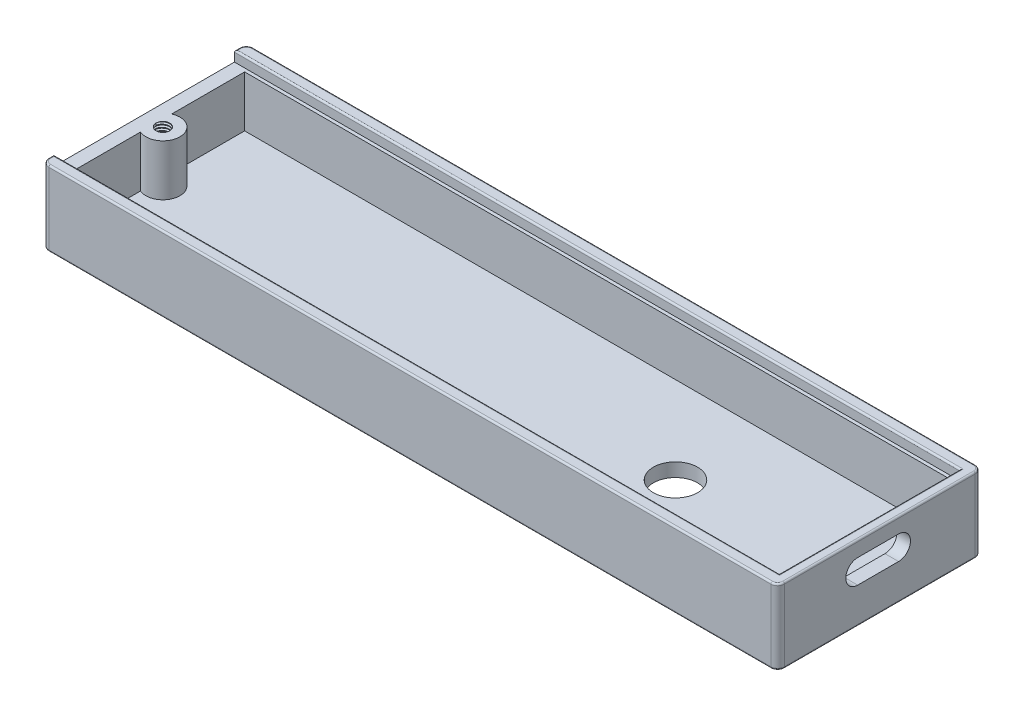
SolidWorks part; units mm, degrees
material "ABS"
ref_plane "Front Plane" through (0, 0, 0) normal (0, 0, 1) x (1, 0, 0)
ref_plane "Top Plane" through (0, 0, 0) normal (0, 1, 0) x (1, 0, 0)
ref_plane "Right Plane" through (0, 0, 0) normal (1, 0, 0) x (0, 0, -1)
sketch "Sketch1" plane through (0, 0, 0) normal (0, 1, 0) x (1, 0, 0)
  line L1 (0, 0) -> (108, 0)
  line L2 (0, 0) -> (0, -30)
  line L3 (0, -30) -> (108, -30)
  line L4 (108, 0) -> (108, -30)
  dimension "D1" = 108
  dimension "D2" = 30
extrude "Boss-Extrude1" add sketch "Sketch1" against normal blind 11
sketch "Sketch2" plane through (0, 0, 0) normal (0, 1, 0) x (1, 0, 0)
  line L0 (0, -30) -> (108, -30) construction
  line L1 (0, -1.75) -> (106.5, -1.75)
  line L2 (0, -1.75) -> (0, -28.25)
  line L3 (0, -28.25) -> (106.5, -28.25)
  line L4 (106.5, -1.75) -> (106.5, -28.25)
  line L6 (108, -30) -> (108, 0) construction
  line L8 (0, 0) -> (0, -30) construction
  line L10 (108, 0) -> (0, 0) construction
  dimension "D1" = 1.75
  dimension "D2" = 1.75
  dimension "D3" = 1.5
extrude "Cut-Extrude1" cut sketch "Sketch2" against normal blind 1.5
sketch "Sketch3" plane through (0, 0, 0) normal (0, 1, 0) x (1, 0, 0)
  line L0 (106.5, -1.75) -> (0, -1.75) construction
  line L1 (2, -2.25) -> (106, -2.25)
  line L2 (2, -2.25) -> (2, -27.75)
  line L3 (2, -27.75) -> (106, -27.75)
  line L4 (106, -2.25) -> (106, -27.75)
  line L5 (106.5, -28.25) -> (106.5, -1.75) construction
  line L6 (0, -28.25) -> (106.5, -28.25) construction
  line L7 (0, -1.75) -> (0, -28.25) construction
  dimension "D1" = 0.5
  dimension "D2" = 0.5
  dimension "D3" = 0.5
  dimension "D4" = 2
extrude "Cut-Extrude2" cut sketch "Sketch3" against normal blind 9
fillet "Fillet1" radius 0.25 12 edges at (0, 0, 0.875) (54, 0, 0) (108, 0, 15) (54, 0, 30) (0, 0, 29.125) (53.25, 0, 28.25) (106.5, 0, 15) (53.25, 0, 1.75) (54, -11, 30) (108, -11, 15) (54, -11, 0) (0, -11, 15)
fillet "Fillet2" radius 1 12 edges at (107.9268, -0.0732, 29.9268) (107.9268, -0.0732, 0.0732) (0.0732, -0.0732, 0.0732) (0.0732, -0.0732, 29.9268) (0, -5.5, 30) (0, -5.5, 0) (108, -5.5, 0) (108, -5.5, 30) (107.9268, -10.9268, 29.9268) (107.9268, -10.9268, 0.0732) (0.0732, -10.9268, 0.0732) (0.0732, -10.9268, 29.9268)
sketch "Sketch4" plane through (0, -9, 0) normal (0, 1, 0) x (1, 0, 0)
  line L0 (0, -1.75) -> (0, -28.25) construction
  line L2 (0, -28.25) -> (106.5, -28.25) construction
  circle A0 centre (3, -15.25) radius 2.5
  dimension "D1" = 5
  dimension "D2" = 3
  dimension "D3" = 13
extrude "Boss-Extrude2" add sketch "Sketch4" along normal up to surface (7.5 mm away) up to face at (54, -1.5, 15)
hole_wizard "Ø2.0 (2) Diameter Hole1" positions "3DSketch1" profile "Sketch5" hole size "Ø2.0" standard "ISO"
sketch3d "3DSketch1"
  line L0 (0, -1.5, 1.75) -> (0, -1.5, 28.25) construction
  point P0 (3, -1.5, 15.25)
  dimension "D1" = 3
  dimension "D2" = 13.5
sketch "Sketch5" plane through (3, -1.5, 15.25) normal (1, 0, 0) x (0, 0, 1)
  line L0 (0, 0) -> (0, 5.6009)
  line L1 (0, 5.6009) -> (1, 5)
  line L2 (1, 5) -> (1, 0)
  line L5 (1, 0) -> (0, 0)
  line L10 (0, 5.6009) -> (-1, 5) construction
  line L11 (0, -6.35) -> (0, 107.95) construction
  dimension "Hole Dia." = 2
  dimension "Hole Depth" = 5
  dimension "Drill Angle" = 118
thread "Thread1" pitch 0.4 method cut profile "Thread Profile1" start angle 0, offset 0, length 4, pitch 0.4, diameter 2
ref_plane "Plane4" through (2, -1.5, 15.25) normal (0, 0, 1) x (-1, 0, 0)
sketch "Thread Profile1" plane through (2, -1.5, 15.25) normal (0, 0, 1) x (-1, 0, 0)
  line L0 (0, 0) -> (0, 0.4) construction
  line L1 (0, 0) -> (0.2165, 0.125)
  line L2 (0.2165, 0.125) -> (0.2165, 0.175)
  line L3 (0.2165, 0.175) -> (0, 0.3)
  line L4 (0.2165, 0.15) -> (0, 0.15) construction
  line L11 (0, 0) -> (0, 0.3)
  point P2 (0, 0)
  dimension "Pitch" = 0.4
  dimension "Profile_Angle" = 60
  dimension "Profile_Land" = 0.05
  dimension "Profile_Height" = 0.2165
sketch "Sketch9" plane through (108, 0, 0) normal (1, 0, 0) x (0, 0, -1)
  line L0 (-18.25, -4) -> (-12.25, -4) construction
  line L1 (-18.25, -2.25) -> (-12.25, -2.25)
  line L2 (-18.25, -5.75) -> (-12.25, -5.75)
  line L5 (-30, -10.75) -> (-30, -0.25) construction
  line L6 (-29, -10.75) -> (-1, -10.75) construction
  arc A0 (-18.25, -2.25) -> (-18.25, -5.75) centre (-18.25, -4) ccw
  arc A1 (-12.25, -5.75) -> (-12.25, -2.25) centre (-12.25, -4) ccw
  point P2 (-15.25, -4)
  dimension "D1" = 6
  dimension "D2" = 6.75
  dimension "D3" = 3.5
  dimension "D4" = 14.75
extrude "Cut-Extrude3" cut sketch "Sketch9" against normal up to next
sketch "Sketch10" plane through (0, -11, 0) normal (0, -1, 0) x (1, 0, 0)
  line L0 (107, 29.75) -> (1, 29.75) construction
  line L1 (0.25, 29) -> (0.25, 1) construction
  line L2 (0.25, 14.75) -> (107.75, 14.75) construction
  line L4 (54, 29.25) -> (54, 0) construction
  circle A0 centre (3.25, 26.75) radius 0.75
  circle A1 centre (3.25, 2.75) radius 0.75
  circle A2 centre (104.75, 2.75) radius 0.75
  circle A3 centre (104.75, 26.75) radius 0.75
  dimension "D3" = 1.5
  dimension "D1" = 3
  dimension "D2" = 3
extrude "Boss-Extrude3" add sketch "Sketch10" along normal blind 0.5
fillet "Fillet3" radius 0.25 4 edges at (3.25, -11.5, 26) (104.75, -11.5, 27.5) (104.75, -11.5, 2) (3.25, -11.5, 3.5)
sketch "Sketch11" plane through (106.5, 0, 0) normal (-1, 0, 0) x (0, 0, 1)
  line L0 (28.25, -1.5) -> (28.25, -0.25) construction
  line L1 (1.75, -1.5) -> (28.25, -1.5)
  line L2 (1.75, -1.5) -> (1.75, -0.875)
  line L3 (1.75, -0.875) -> (28.25, -0.875)
  line L4 (28.25, -1.5) -> (28.25, -0.875)
extrude "Cut-Extrude4" cut sketch "Sketch11" against normal blind 1
sketch "Sketch13" plane through (0, -9, 0) normal (0, 1, 0) x (1, 0, 0)
  line L0 (106, -27.75) -> (106, -2.25) construction
  line L2 (1, -30) -> (107, -30) construction
  circle A0 centre (78, -15) radius 3.25
  dimension "D1" = 6.5
  dimension "D2" = 28
  dimension "D3" = 15
extrude "Cut-Extrude5" cut sketch "Sketch13" against normal through all
